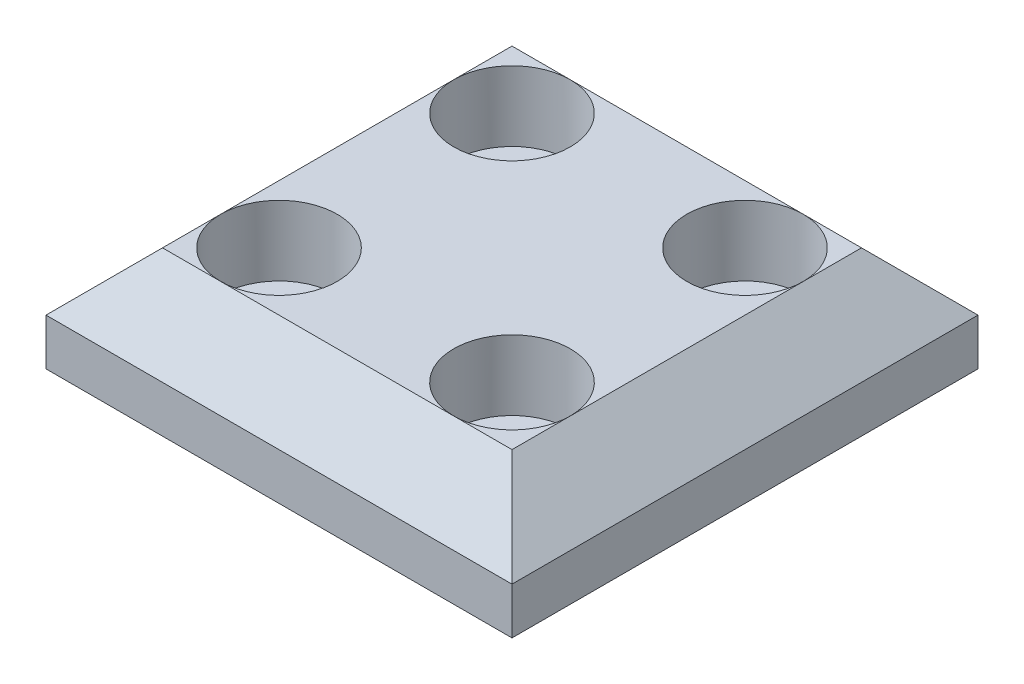
SolidWorks part; units mm, degrees
ref_plane "Front Plane" through (0, 0, 0) normal (0, 0, 1) x (1, 0, 0)
ref_plane "Top Plane" through (0, 0, 0) normal (0, 1, 0) x (1, 0, 0)
ref_plane "Right Plane" through (0, 0, 0) normal (1, 0, 0) x (0, 0, -1)
sketch "Sketch1" plane through (0, 0, 0) normal (0, 1, 0) x (1, 0, 0)
  line L1 (0, 0) -> (40, 0)
  line L2 (0, 0) -> (0, 40)
  line L3 (0, 40) -> (40, 40)
  line L4 (40, 0) -> (40, 40)
  circle A0 centre (10, 30) radius 2.75
  circle A1 centre (30, 30) radius 2.75
  circle A2 centre (30, 10) radius 2.75
  circle A3 centre (10, 10) radius 2.75
  point P13 (20, 40)
  point P14 (40, 20)
  dimension "D6" = 5.5
  dimension "D1" = 40
  dimension "D2" = 20
  dimension "D3" = 10
  dimension "D4" = 10
  dimension "D5" = 20
extrude "Boss-Extrude1" add sketch "Sketch1" along normal blind 9
sketch "Sketch2" plane through (0, 9, 0) normal (0, 1, 0) x (1, 0, 0)
  circle A0 centre (10, 10) radius 5
  circle A1 centre (30, 10) radius 5
  circle A2 centre (30, 30) radius 5
  circle A3 centre (10, 30) radius 5
  dimension "D1" = 10
extrude "Cut-Extrude1" cut sketch "Sketch2" against normal blind 6
chamfer "Chamfer1" distance 5 angle 45 4 edges at (20, 9, -40) (40, 9, -20) (20, 9, 0) (0, 9, -20)
